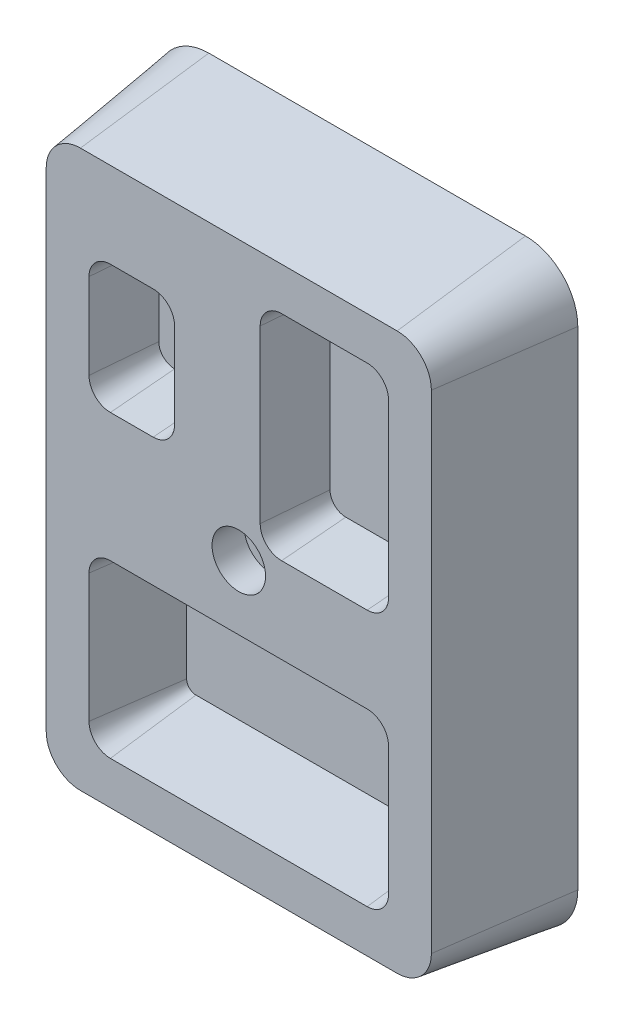
SolidWorks part; units mm, degrees
ref_plane "Front Plane" through (0, 0, 0) normal (1, 0, 0) x (0, 1, 0)
ref_plane "Top Plane" through (0, 0, 0) normal (0, 0, 1) x (0, 1, 0)
ref_plane "Right Plane" through (0, 0, 0) normal (0, 1, 0) x (-1, 0, 0)
sketch "Sketch1" plane through (0, 0, 0) normal (0, 0, 1) x (0, 1, 0)
  line L1 (-72.39, 57.15) -> (72.39, 57.15)
  line L2 (-82.55, 46.99) -> (-82.55, -46.99)
  line L3 (-72.39, -57.15) -> (72.39, -57.15)
  line L4 (82.55, 46.99) -> (82.55, -46.99)
  line L5 (-82.55, 57.15) -> (82.55, -57.15) construction
  line L6 (-82.55, -57.15) -> (82.55, 57.15) construction
  arc A0 (-72.39, 57.15) -> (-82.55, 46.99) centre (-72.39, 46.99) ccw
  arc A1 (-82.55, -46.99) -> (-72.39, -57.15) centre (-72.39, -46.99) ccw
  arc A2 (72.39, -57.15) -> (82.55, -46.99) centre (72.39, -46.99) ccw
  arc A3 (72.39, 57.15) -> (82.55, 46.99) centre (72.39, 46.99) cw
  point P0 (0, 0)
  dimension "D3" = 10.16
  dimension "D1" = 114.3
  dimension "D2" = 165.1
extrude "Boss-Extrude1" add sketch "Sketch1" against normal blind 38.1 draft 8 contours L1 A3 L4 A2 L3 A1 L2 A0 draft outward yes
sketch "Sketch4" plane through (0, 0, 0) normal (0, 0, 1) x (0, 1, 0)
  line L0 (-82.55, 46.99) -> (-82.55, -46.99) construction
  line L1 (-63.5, 44.45) -> (-25.4, 44.45)
  line L2 (-69.85, 38.1) -> (-69.85, -38.1)
  line L3 (-63.5, -44.45) -> (-25.4, -44.45)
  line L4 (-19.05, 38.1) -> (-19.05, -38.1)
  line L5 (-44.45, -44.45) -> (-44.45, 44.45) construction
  line L6 (-69.85, 0) -> (-19.05, 0) construction
  line L7 (25.4, 44.45) -> (50.8, 44.45)
  line L8 (19.05, 38.1) -> (19.05, 25.4)
  line L9 (25.4, 19.05) -> (50.8, 19.05)
  line L10 (57.15, 38.1) -> (57.15, 25.4)
  line L11 (38.1, 19.05) -> (38.1, 44.45) construction
  line L12 (19.05, 31.75) -> (57.15, 31.75) construction
  line L13 (12.7, -6.35) -> (63.5, -6.35)
  line L14 (6.35, -12.7) -> (6.35, -38.1)
  line L15 (12.7, -44.45) -> (63.5, -44.45)
  line L16 (69.85, -12.7) -> (69.85, -38.1)
  line L17 (38.1, -44.45) -> (38.1, -6.35) construction
  line L18 (6.35, -25.4) -> (69.85, -25.4) construction
  line L19 (82.55, 46.99) -> (82.55, -46.99) construction
  arc A0 (50.8, 44.45) -> (57.15, 38.1) centre (50.8, 38.1) cw
  arc A1 (25.4, 44.45) -> (19.05, 38.1) centre (25.4, 38.1) ccw
  arc A2 (19.05, 25.4) -> (25.4, 19.05) centre (25.4, 25.4) ccw
  arc A3 (50.8, 19.05) -> (57.15, 25.4) centre (50.8, 25.4) ccw
  arc A4 (63.5, -44.45) -> (69.85, -38.1) centre (63.5, -38.1) ccw
  arc A5 (63.5, -6.35) -> (69.85, -12.7) centre (63.5, -12.7) cw
  arc A6 (12.7, -6.35) -> (6.35, -12.7) centre (12.7, -12.7) ccw
  arc A7 (6.35, -38.1) -> (12.7, -44.45) centre (12.7, -38.1) ccw
  arc A8 (-25.4, -44.45) -> (-19.05, -38.1) centre (-25.4, -38.1) ccw
  arc A9 (-69.85, -38.1) -> (-63.5, -44.45) centre (-63.5, -38.1) ccw
  arc A10 (-25.4, 44.45) -> (-19.05, 38.1) centre (-25.4, 38.1) cw
  arc A11 (-63.5, 44.45) -> (-69.85, 38.1) centre (-63.5, 38.1) ccw
  point P0 (-44.45, 0)
  point P4 (38.1, 31.75)
  point P8 (38.1, -25.4)
  dimension "D9" = 6.35
  dimension "D1" = 88.9
  dimension "D2" = 50.8
  dimension "D3" = 12.7
  dimension "D4" = 25.4
  dimension "D5" = 38.1
  dimension "D6" = 63.5
  dimension "D7" = 38.1
  dimension "D8" = 12.7
extrude "Cut-Extrude1" cut sketch "Sketch4" against normal blind 19.05 draft 5 contours L9 A3 L10 A0 L7 A1 L8 A2 | L14 A7 L15 A4 L16 A5 L13 A6 region at (-31.75, 38.1, 0) region at (25.4, 38.1, 0)
extrude "Cut-Extrude2" cut sketch "Sketch4<3>" against normal blind 25.4 draft 8 contours L1 A11 L2 A9 L3 A8 L4 A10 region at (0, -44.45, 0)
sketch "Sketch4<3>" plane through (0, 0, 0) normal (0, 0, 1) x (0, 1, 0) same geometry as "Sketch4"
hole_wizard "CBORE for 3/8 Socket Head Cap Screw1" positions "Sketch5" profile "Sketch7" counterbore size "3/8" standard "ANSI Inch" end condition through all
sketch "Sketch5" plane through (0, 0, 0) normal (0, 0, 1) x (0, -1, 0)
  point P0 (0, 0)
sketch "Sketch7" plane through (0, 0, 0) normal (1, 0, 0) x (0, -1, 0)
  line L0 (0, 0) -> (0, 38.1)
  line L1 (0, 38.1) -> (5.1562, 38.1)
  line L3 (5.1562, 38.1) -> (5.1562, 9.525)
  line L4 (5.1562, 9.525) -> (7.9375, 9.525)
  line L5 (7.9375, 9.525) -> (7.9375, 0)
  line L7 (7.9375, 0) -> (0, 0)
  line L11 (0, -6.35) -> (0, 107.95) construction
  dimension "Thru Hole Dia." = 10.3124
  dimension "Thru Hole Depth" = 38.1
  dimension "C'Bore Dia." = 15.875
  dimension "C'Bore Depth" = 9.525
